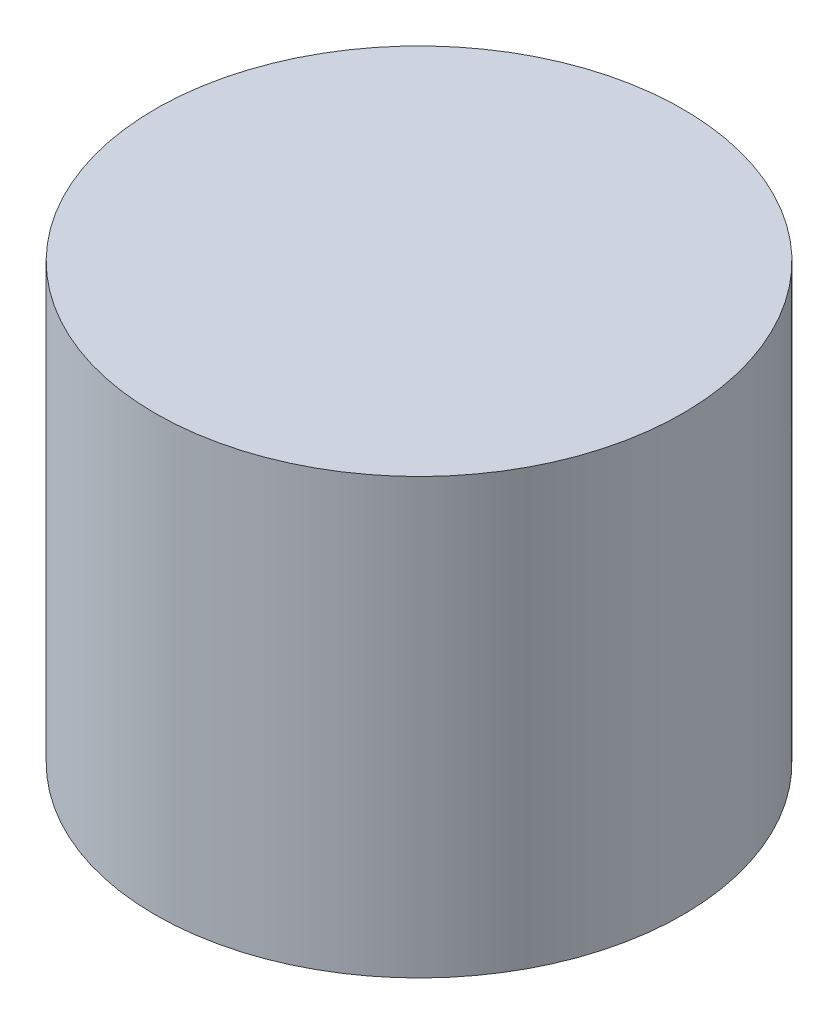
SolidWorks part; units mm, degrees
ref_plane "Front" through (0, 0, 0) normal (0, 0, 1) x (1, 0, 0)
ref_plane "Top" through (0, 0, 0) normal (0, 1, 0) x (1, 0, 0)
ref_plane "Right" through (0, 0, 0) normal (1, 0, 0) x (0, 0, -1)
sketch "Sketch1" plane through (0, 0, 0) normal (0, 1, 0) x (1, 0, 0)
  circle A0 centre (0, 0) radius 1.7
  dimension "D1" = 3.4
extrude "Boss-Extrude1" add sketch "Sketch1" along normal blind 1.4 and the other way blind 1.4
